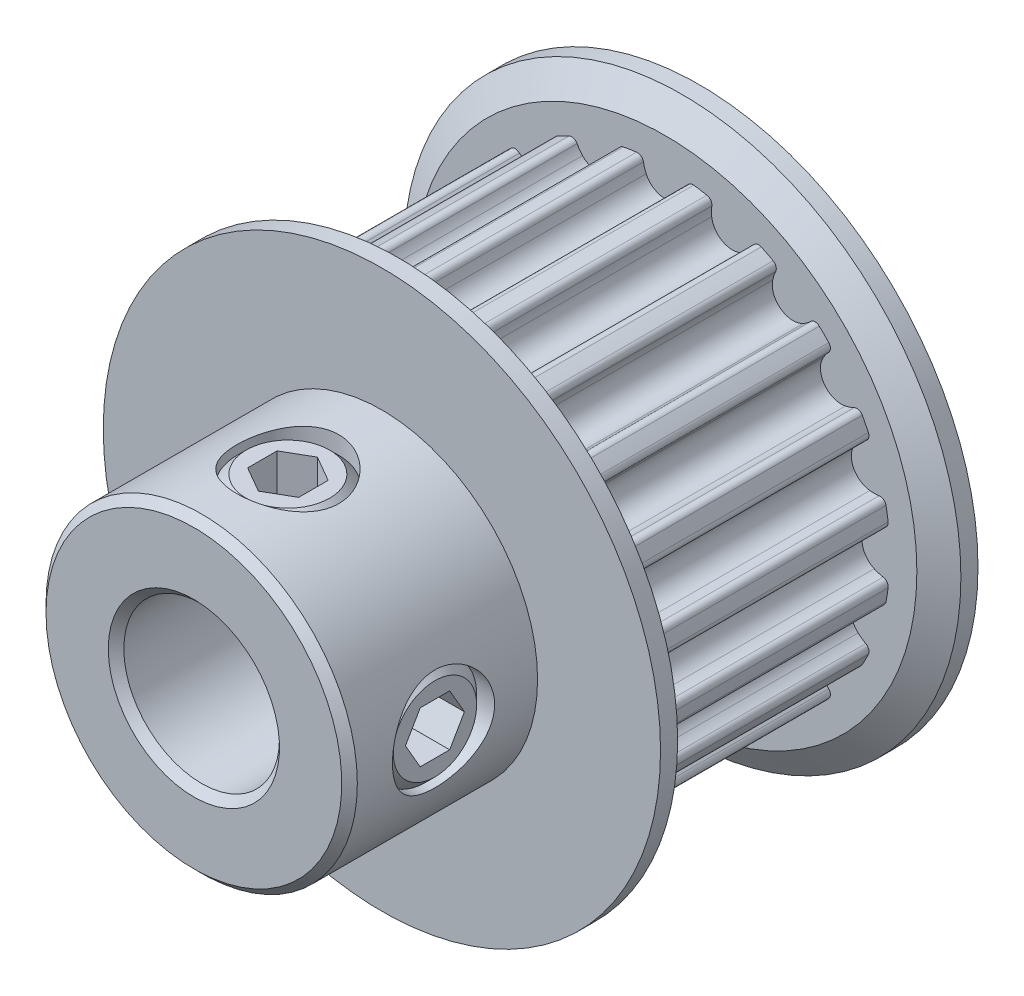
SolidWorks part; units mm, degrees
ref_plane "Front Plane" through (0, 0, 0) normal (0, 0, 1) x (1, 0, 0)
ref_plane "Top Plane" through (0, 0, 0) normal (0, 1, 0) x (1, 0, 0)
ref_plane "Right Plane" through (0, 0, 0) normal (1, 0, 0) x (0, 0, -1)
sketch "Sketch1" plane through (0, 0, 0) normal (0, 0, 1) x (1, 0, 0)
  line L1 (-2.6202, 8.0295) -> (2.6202, 8.0295) construction
  line L4 (0, 0) -> (0, 8.0295) construction
  line L5 (0, 8.0295) -> (0, 12.595) construction
  line L6 (0, 9.5505) -> (2.9628, 9.0793) construction
  line L7 (2.9628, 9.0793) -> (4.0126, 8.7367) construction
  line L8 (2.9628, 9.0793) -> (2.6202, 8.0295) construction
  line L9 (-2.9628, 9.0793) -> (-2.6202, 8.0295) construction
  line L10 (-2.8446, 8.7171) -> (-3.7091, 11.3665)
  line L11 (-3.7091, 11.3665) -> (3.7091, 11.3665)
  line L12 (3.7091, 11.3665) -> (2.8446, 8.7171)
  circle A0 centre (0, 0) radius 9.5505 construction
  circle A1 centre (0, 0) radius 11.3665 construction
  circle A2 centre (0, 0) radius 9.1695 construction
  arc A3 (-0.7739, 8.5279) -> (0.7739, 8.5279) centre (0, 8.8795) ccw
  arc A4 (-0.7739, 8.5279) -> (-0.8866, 8.891) centre (0.61, 9.1566) cw
  arc A5 (-2.8446, 8.7171) -> (-1.1645, 9.0953) centre (0, 0) cw
  arc A6 (-0.8866, 8.891) -> (-1.1645, 9.0953) centre (-1.1328, 8.8473) ccw
  arc A7 (2.8446, 8.7171) -> (1.1645, 9.0953) centre (0, 0) ccw
  arc A8 (0.8866, 8.891) -> (1.1645, 9.0953) centre (1.1328, 8.8473) cw
  arc A9 (0.7739, 8.5279) -> (0.8866, 8.891) centre (-0.61, 9.1566) ccw
  point P6 (0, 20.9083)
  point P11 (0, 9.5505)
  point P13 (0, 11.3665)
  point P14 (0, 9.1695)
  dimension "D1" = 8.3133
  dimension "D2" = 3.0445
sketch "Sketch2" plane through (0, 0, 0) normal (1, 0, 0) x (0, 0, -1)
  line L0 (-10.31, 3.175) -> (10.31, 3.175)
  line L1 (-10.31, 3.175) -> (-10.31, 6.35)
  line L2 (-10.31, 6.35) -> (-2.64, 6.35)
  line L3 (-2.64, 6.35) -> (-2.64, 11.3665)
  line L4 (-2.64, 11.3665) -> (-1.245, 11.3665) construction
  line L5 (-1.245, 11.3665) -> (-1.245, 9.1695) construction
  line L6 (-1.245, 9.1695) -> (8.915, 9.1695)
  line L7 (8.915, 9.1695) -> (8.915, 11.3665) construction
  line L8 (8.915, 11.3665) -> (10.31, 11.3665) construction
  line L9 (10.31, 11.3665) -> (10.31, 3.175)
  line L10 (-10.31, 0) -> (10.31, 0) construction
  line L11 (9.6125, 11.3665) -> (8.915, 10.268)
  line L12 (-1.245, 10.268) -> (-1.9425, 11.3665)
  line L13 (-2.64, 11.3665) -> (-1.9425, 11.3665)
  line L14 (-1.245, 10.268) -> (-1.245, 9.1695)
  line L15 (8.915, 9.1695) -> (8.915, 10.268)
  line L16 (9.6125, 11.3665) -> (10.31, 11.3665)
  arc A0 (-1.245, 10.268) -> (-1.9425, 11.3665) centre (-2.4588, 10.268) ccw construction
  arc A1 (8.915, 10.268) -> (9.6125, 11.3665) centre (10.1288, 10.268) cw construction
  point P12 (-1.245, 10.268)
  point P14 (-1.9425, 11.3665)
  point P20 (8.915, 10.268)
  point P21 (9.6125, 11.3665)
  point P25 (8.915, 0)
  point P26 (-1.245, 0)
revolve "Revolve1" add sketch "Sketch2" angle 360 mid plane about L10
sketch "Sketch3" plane through (0, 0, 0) normal (0, 0, 1) x (1, 0, 0)
  line L6 (3.7091, 11.3665) -> (-3.7091, 11.3665)
  line L7 (2.8446, 8.7171) -> (3.7091, 11.3665)
  line L8 (-3.7091, 11.3665) -> (-2.8446, 8.7171)
  line L9 (3.7091, 11.3665) -> (-3.7091, 11.3665)
  line L10 (2.8446, 8.7171) -> (3.7091, 11.3665)
  line L11 (-3.7091, 11.3665) -> (-2.8446, 8.7171)
  arc A8 (2.8446, 8.7171) -> (1.1645, 9.0953) centre (0, 0) ccw
  arc A9 (1.1645, 9.0953) -> (0.8866, 8.891) centre (1.1328, 8.8473) ccw
  arc A10 (0.7739, 8.5279) -> (0.8866, 8.891) centre (-0.61, 9.1566) ccw
  arc A11 (-0.7739, 8.5279) -> (0.7739, 8.5279) centre (0, 8.8795) ccw
  arc A12 (-0.8866, 8.891) -> (-0.7739, 8.5279) centre (0.61, 9.1566) ccw
  arc A13 (-0.8866, 8.891) -> (-1.1645, 9.0953) centre (-1.1328, 8.8473) ccw
  arc A14 (-1.1645, 9.0953) -> (-2.8446, 8.7171) centre (0, 0) ccw
  arc A15 (2.8446, 8.7171) -> (1.1645, 9.0953) centre (0, 0) ccw
  arc A16 (1.1645, 9.0953) -> (0.8866, 8.891) centre (1.1328, 8.8473) ccw
  arc A17 (0.7739, 8.5279) -> (0.8866, 8.891) centre (-0.61, 9.1566) ccw
  arc A18 (-0.7739, 8.5279) -> (0.7739, 8.5279) centre (0, 8.8795) ccw
  arc A19 (-0.8866, 8.891) -> (-0.7739, 8.5279) centre (0.61, 9.1566) ccw
  arc A20 (-0.8866, 8.891) -> (-1.1645, 9.0953) centre (-1.1328, 8.8473) ccw
  arc A21 (-1.1645, 9.0953) -> (-2.8446, 8.7171) centre (0, 0) ccw
  dimension "D1" = 0
extrude "Cut-Extrude1" cut sketch "Sketch3" against normal up to vertex (8.915 mm away) from vertex up to point (0, 9.1695, -8.915) starting at point (0, 9.1695, 1.245)
pattern_circular "CirPattern1" count 20 over 360 about axis through (0, 0, 10.31) along (0, 0, 1) of "Cut-Extrude1"
sketch "Sketch4" plane through (0, 0, 0) normal (1, 0, 0) x (0, -1, 0)
  line L0 (0, -2.64) -> (0, -10.31) construction
  line L1 (-6.35, -2.64) -> (6.35, -2.64) construction
  line L2 (-6.35, -10.31) -> (6.35, -10.31) construction
  circle A0 centre (0, -6.475) radius 2.0828
extrude "Cut-Extrude2" cut sketch "Sketch4" along normal through all
ref_plane "Plane1" through (0, 0, 6.475) normal (0, 0, 1) x (1, 0, 0)
sketch "Sketch5" plane through (0, 0, 6.475) normal (0, 0, 1) x (1, 0, 0)
  line L0 (0, 0.1664) -> (0, 6.35) construction
  line L1 (3.175, -1.7018) -> (3.175, 0)
  line L2 (3.556, -2.0828) -> (5.6177, -2.0828)
  line L3 (3.175, 0) -> (6.35, 0) construction
  line L4 (3.175, 0) -> (5.9987, 0)
  line L5 (5.9987, 0) -> (5.9987, -1.7018)
  line L6 (3.556, -2.0828) -> (3.175, -1.7018)
  line L7 (5.9987, -1.7018) -> (5.6177, -2.0828)
  circle A0 centre (0, 0) radius 6.35 construction
  circle A1 centre (0, 0) radius 3.175 construction
  point P2 (3.175, -2.0828)
  point P11 (5.9987, -2.0828)
revolve "Revolve2" add sketch "Sketch5" angle 360 mid plane about L4
sketch "Sketch6" plane through (5.9987, 5.3841, 0) normal (-1, 0, 0) x (0, -1, 0)
  line L1 (5.3841, 7.6775) -> (4.3427, 7.0763)
  line L2 (4.3427, 7.0763) -> (4.3427, 5.8737)
  line L3 (4.3427, 5.8737) -> (5.3841, 5.2725)
  line L4 (5.3841, 5.2725) -> (6.4255, 5.8737)
  line L5 (6.4255, 5.8737) -> (6.4255, 7.0763)
  line L6 (6.4255, 7.0763) -> (5.3841, 7.6775)
  circle A0 centre (5.3841, 6.475) radius 1.0414 construction
  dimension "D1" = 2.0828
extrude "Cut-Extrude3" cut sketch "Sketch6" along normal blind 1.5621
pattern_circular "CirPattern2" count 2 over 90 about axis through (0, 0, 10.31) along (0, 0, 1) of "Cut-Extrude2", "Revolve2", "Cut-Extrude3"
chamfer "Chamfer1" distance 0.3175 angle 45 2 edges at (3.175, 0, 10.31) (6.35, 0, 10.31)
ref_axis "Center Axis 1" through (0, 0, -10.31) along (0, 0, 1)
ref_plane "Contact Plane 1" through (0, 0, 10.31) normal (0, 0, 1) x (1, 0, 0)
ref_plane "Contact Plane 2" through (0, 0, -10.31) normal (0, 0, -1) x (-1, 0, 0)
equation "\"D2@Sketch1\" = \"D1@Sketch1\"/2"
equation "\"D1@Sketch6\" = \"Set Screw@Sketch4\" / 2"
equation "\"D1@Cut-Extrude3\" = \"D1@Sketch6\"*.75"
equation "\"D1@Chamfer1\"=\"Hub Dia@Sketch2\"*.025"
